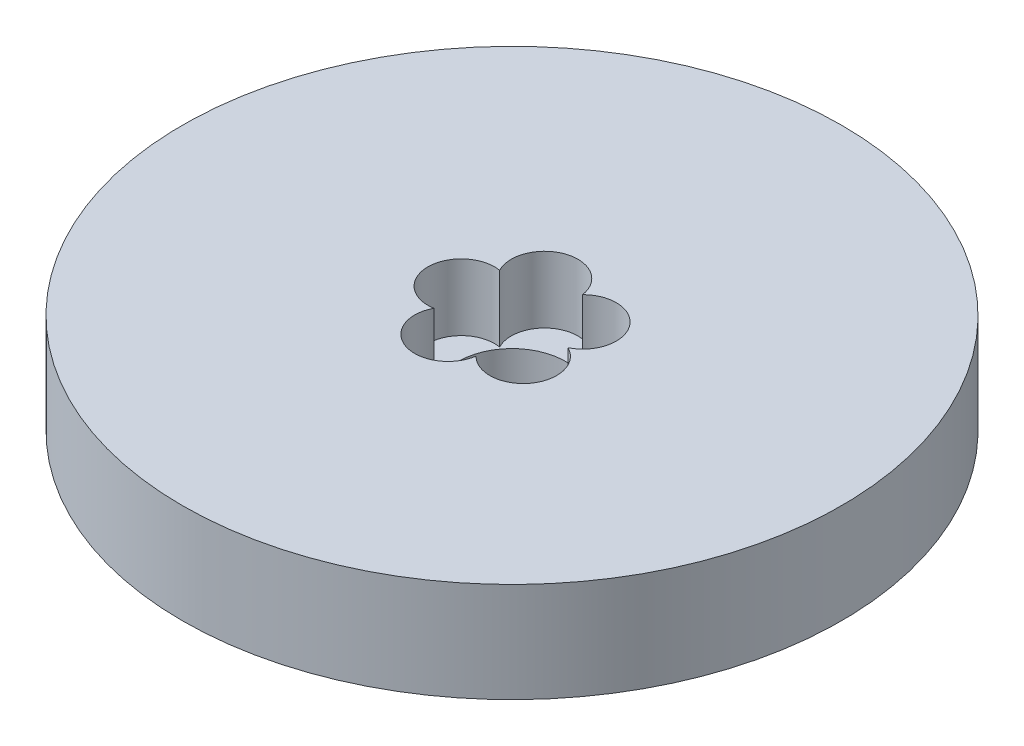
SolidWorks part; units mm, degrees
ref_plane "Front Plane" through (0, 0, 0) normal (0, 0, 1) x (1, 0, 0)
ref_plane "Top Plane" through (0, 0, 0) normal (0, 1, 0) x (1, 0, 0)
ref_plane "Right Plane" through (0, 0, 0) normal (1, 0, 0) x (0, 0, -1)
sketch "Sketch1" plane through (0, 0, 0) normal (0, 1, 0) x (1, 0, 0)
  circle A0 centre (0, 0) radius 92.5
  dimension "FLANGE_OD" = 185
extrude "Boss-Extrude1" add sketch "Sketch1" along normal blind 28
sketch "Sketch2" plane through (0, 0, 0) normal (0, 1, 0) x (1, 0, 0)
  circle A0 centre (0, 0) radius 15
  dimension "BORE_D" = 30
extrude "Cut-Extrude1" cut sketch "Sketch2" along normal through all
sketch "Sketch3" plane through (0, 28, 0) normal (0, 1, 0) x (1, 0, 0)
  circle A0 centre (0, 0) radius 14.2499 construction
  circle A1 centre (-14.2499, 0) radius 9.3664
  dimension "BOLT_D" = 18.7327
  dimension "BOLT_PCD" = 28.4997
extrude "Cut-Extrude2" cut sketch "Sketch3" against normal blind 18.6585
pattern_circular "CirPattern1" count 5 over 360 about axis through (0, 0, 0) along (0, 1, 0) of "Cut-Extrude2"
